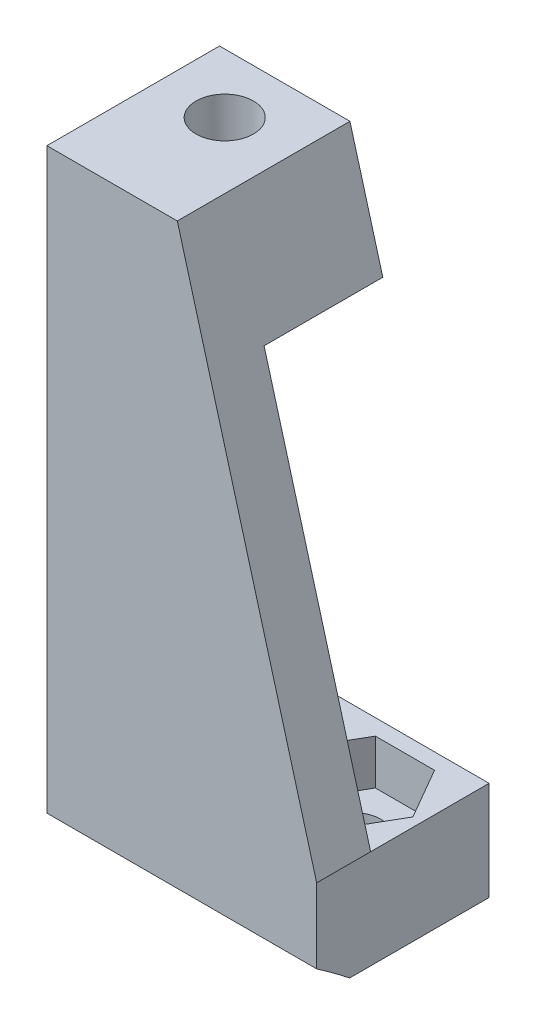
SolidWorks part; units mm, degrees
ref_plane "Front Plane" through (0, 0, 0) normal (0, 0, 1) x (1, 0, 0)
ref_plane "Top Plane" through (0, 0, 0) normal (0, 1, 0) x (1, 0, 0)
ref_plane "Right Plane" through (0, 0, 0) normal (1, 0, 0) x (0, 0, -1)
sketch "Sketch1" plane through (-20.2227, 0, 0) normal (-1, 0, 0) x (0, 0, 1)
  line L2 (137.6702, 40.71) -> (137.6702, 37.11)
  line L4 (137.6702, 37.11) -> (144.2702, 37.11)
  line L7 (137.6702, 38.11) -> (144.2702, 38.11)
  line L13 (137.6827, 10.21) -> (145.4336, 10.21)
  line L15 (145.5956, 10.21) -> (137.3827, 10.21) construction
  line L16 (147.2702, 11.5665) -> (147.2702, 43.71)
  line L18 (147.2702, 43.71) -> (137.6702, 43.71)
  line L20 (137.6702, 43.71) -> (137.6702, 40.71)
  line L21 (137.6702, 40.71) -> (144.2702, 40.71)
  line L22 (144.2702, 40.71) -> (144.2702, 13.21)
  line L23 (144.2702, 13.21) -> (137.6827, 13.21)
  line L25 (137.6827, 13.21) -> (137.6827, 10.21)
  line L26 (140.9702, 43.71) -> (140.9702, 40.71) construction
  line L27 (142.5577, 43.71) -> (142.5577, 45.71) construction
  line L28 (139.3827, 45.71) -> (139.3827, 43.71) construction
  line L29 (140.9764, 13.21) -> (140.9764, 10.21) construction
  line L30 (137.3827, 10.21) -> (137.3827, 19.4857) construction
  line L32 (180.8827, 43.71) -> (137.8827, 43.71) construction
  arc A0 (145.4336, 10.21) -> (147.2702, 11.5665) centre (168.3827, -18.9405) cw
  arc A1 (191.1698, 10.21) -> (145.5956, 10.21) centre (168.3827, -18.9405) ccw construction
  line M34 (145.5956, 10.21) -> (137.3827, 10.21)
  dimension "D1" = 0.1
  dimension "D2" = 6.6
  dimension "D3" = 0.3
  dimension "D4" = 3
  dimension "D5" = 3
  dimension "D6" = 3
  dimension "D7" = 1
  dimension "D8" = 2.6
extrude "Boss-Extrude1" add sketch "Sketch1" against normal blind 15 contours A0 L16 L18 L20 L21 L22 L23 L25 M34 | L22 L21 L2 L4 | L22 L7 L2 L4 region at (-20.2227, 39.41, 140.9702) region at (-20.2227, 27.1135, 144.3947) region at (-20.2227, 37.61, 140.9702)
sketch "Sketch3" plane through (0, 37.11, 0) normal (0, -1, 0) x (1, 0, 0)
  line L1 (-16.6352, 137.6793) -> (-13.7852, 139.3247)
  line L2 (-13.7852, 139.3247) -> (-13.7852, 142.6156)
  line L3 (-13.7852, 142.6156) -> (-16.6352, 144.2611)
  line L4 (-16.6352, 144.2611) -> (-19.4852, 142.6156)
  line L5 (-19.4852, 142.6156) -> (-19.4852, 139.3247)
  line L6 (-19.4852, 139.3247) -> (-16.6352, 137.6793)
  line L8 (-20.2227, 145.4336) -> (-20.2227, 137.6827) construction
  line L9 (-19.4852, 139.3247) -> (-19.4852, 137.6702)
  line L11 (-13.7852, 139.3247) -> (-13.7852, 137.6702)
  line L12 (-19.4852, 137.6702) -> (-13.7852, 137.6702)
  line L13 (-5.2227, 137.6702) -> (-20.2227, 137.6702) construction
  circle A0 centre (-16.6352, 140.9702) radius 1.5956 construction
  circle A1 centre (-16.6352, 140.9702) radius 1.5956
  circle A2 centre (-16.6352, 140.9702) radius 2.85 construction
  dimension "D1" = 5.7
extrude "Cut-Extrude2" cut sketch "Sketch3" against normal up to next contours A1 region at (-16.6352, 37.11, 140.9702)
extrude "Cut-Extrude5" cut sketch "Sketch3<6>" against normal up to vertex (3.6 mm away) from vertex contours L6 L12 L1 L2 L3 L4 L5 A1 | L9 L12 L6 | L1 L12 L11 region at (-18.0167, 37.11, 138.5774) region at (-15.1805, 37.11, 138.4506) up to point (-20.2227, 40.71, 137.6702) starting at point (-20.2227, 38.11, 137.6702)
sketch "Sketch3<6>" plane through (0, 37.11, 0) normal (0, -1, 0) x (1, 0, 0) same geometry as "Sketch3"
sketch "Sketch4" plane through (0, 13.21, 0) normal (0, 1, 0) x (1, 0, 0)
  line L0 (-20.2227, -147.2702) -> (-20.2227, -137.6702) construction
  line L3 (-12.7227, -137.6827) -> (-12.7227, -144.2702) construction
  line L4 (-5.2227, -137.6827) -> (-20.2227, -137.6827) construction
  line L5 (-5.2227, -144.2702) -> (-20.2227, -144.2702) construction
  line L6 (-13.1409, -141.4202) -> (-14.7864, -138.5702)
  line L7 (-14.7864, -138.5702) -> (-18.0773, -138.5702)
  line L8 (-18.0773, -138.5702) -> (-19.7227, -141.4202)
  line L9 (-19.7227, -141.4202) -> (-18.0773, -144.2702)
  line L10 (-18.0773, -144.2702) -> (-14.7864, -144.2702)
  line L11 (-14.7864, -144.2702) -> (-13.1409, -141.4202)
  line L12 (-5.7227, -141.4202) -> (-7.3682, -138.5702)
  line L13 (-7.3682, -138.5702) -> (-10.6591, -138.5702)
  line L14 (-10.6591, -138.5702) -> (-12.3045, -141.4202)
  line L15 (-12.3045, -141.4202) -> (-10.6591, -144.2702)
  line L16 (-10.6591, -144.2702) -> (-7.3682, -144.2702)
  line L17 (-7.3682, -144.2702) -> (-5.7227, -141.4202)
  circle A0 centre (-16.4318, -141.4202) radius 1.5
  circle A1 centre (-9.0136, -141.4202) radius 1.5
  circle A2 centre (-16.4318, -141.4202) radius 2.85 construction
  circle A3 centre (-9.0136, -141.4202) radius 2.85 construction
  dimension "D1" = 3
  dimension "D2" = 0.5
  dimension "D3" = 5.7
extrude "Cut-Extrude3" cut sketch "Sketch4" against normal up to next contours A0 | A1 region at (-16.4318, 13.21, 141.4202) region at (-9.0136, 13.21, 141.4202)
sketch "Sketch11" plane through (0, 13.21, 0) normal (0, 1, 0) x (1, 0, 0)
  line L0 (-19.7227, -141.4202) -> (-18.0773, -144.2702)
  line L1 (-18.0773, -144.2702) -> (-14.7864, -144.2702)
  line L2 (-14.7864, -144.2702) -> (-13.1409, -141.4202)
  line L3 (-13.1409, -141.4202) -> (-14.7864, -138.5702)
  line L4 (-14.7864, -138.5702) -> (-18.0773, -138.5702)
  line L5 (-18.0773, -138.5702) -> (-19.7227, -141.4202)
  line L6 (-10.6591, -144.2702) -> (-7.3682, -144.2702)
  line L7 (-7.3682, -144.2702) -> (-5.7227, -141.4202)
  line L8 (-5.7227, -141.4202) -> (-7.3682, -138.5702)
  line L9 (-7.3682, -138.5702) -> (-10.6591, -138.5702)
  line L10 (-10.6591, -138.5702) -> (-12.3045, -141.4202)
  line L11 (-12.3045, -141.4202) -> (-10.6591, -144.2702)
  line L12 (-5.2227, -137.6827) -> (-5.2227, -144.2702)
  line L14 (-5.2227, -137.6827) -> (-20.2227, -137.6827) construction
  line M9 (-20.2227, -137.6827) -> (-20.2227, -144.2702)
  line M10 (-20.2227, -144.2702) -> (-5.2227, -144.2702)
  line M24 (-5.2227, -137.6827) -> (-20.2227, -137.6827)
extrude "Boss-Extrude10" add sketch "Sketch11" along normal blind 2.5 contours L12 L0 L5 L4 L3 L2 L11 L10 L9 L8 L7 M24 M9 M10 region at (-12.7227, 13.21, 140.3894)
sketch "Sketch2" plane through (0, 0, 147.2702) normal (0, 0, 1) x (1, 0, 0)
  line L0 (-12.9727, 43.71) -> (-5.2227, 15.71)
  line L1 (-5.2227, 43.71) -> (-20.2227, 43.71) construction
  line L3 (-5.2227, 37.11) -> (-5.2227, 15.71) construction
  line L4 (-12.9727, 43.71) -> (-5.2227, 43.71)
  line L5 (-5.2227, 43.71) -> (-5.2227, 15.71)
  line L6 (-5.2227, 11.5665) -> (-5.2227, 43.71) construction
  dimension "D1" = 1.25
extrude "Cut-Extrude1" cut sketch "Sketch2" against normal through all
